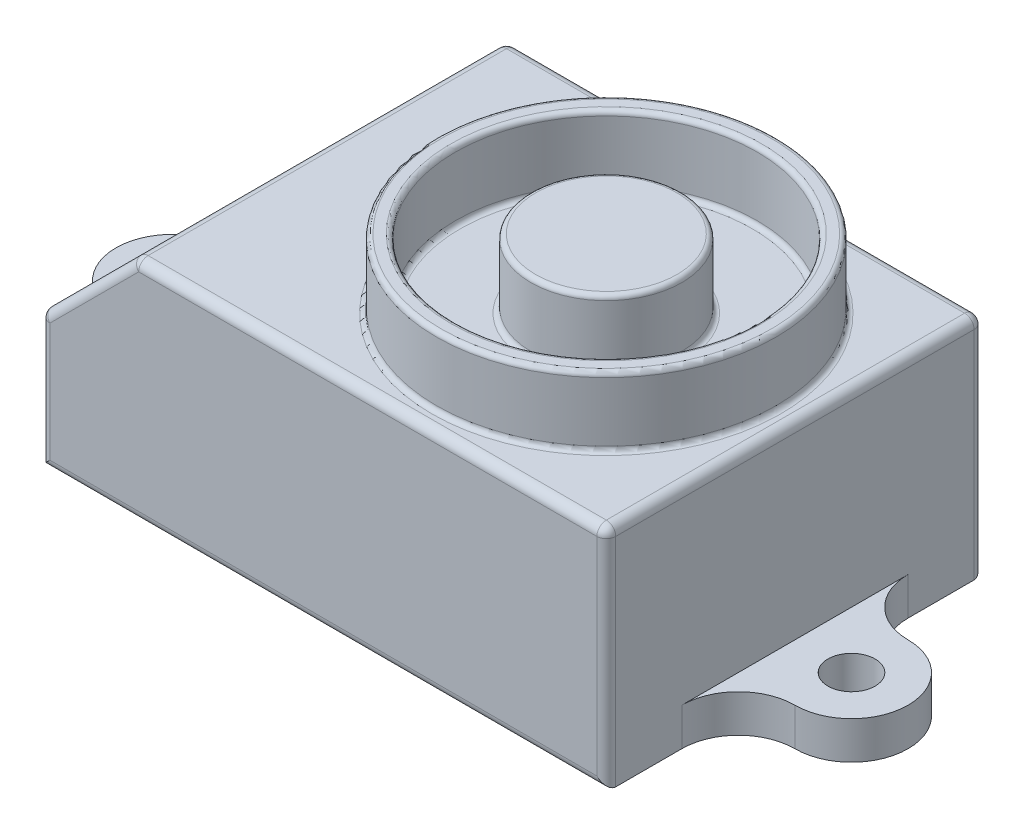
SolidWorks part; units mm, degrees
material "AISI 304"
ref_plane "Plano frontal" through (0, 0, 0) normal (0, 0, 1) x (1, 0, 0)
ref_plane "Plano superior" through (0, 0, 0) normal (0, 1, 0) x (1, 0, 0)
ref_plane "Plano direito" through (0, 0, 0) normal (1, 0, 0) x (0, 0, -1)
sketch "Esboço1" plane through (0, 0, 0) normal (0, 1, 0) x (1, 0, 0)
  line L0 (0, 15.4127) -> (0, -21.5735) construction
  line L1 (-15, 10) -> (15, 10)
  line L2 (-15, 10) -> (-15, -10)
  line L3 (-15, -10) -> (15, -10)
  line L4 (15, 10) -> (15, -10)
  line L5 (-15, 10) -> (15, -10) construction
  line L6 (-15, -10) -> (15, 10) construction
  line L7 (-34.0148, 0) -> (34.7521, 0) construction
  arc A0 (-18, 3) -> (-18, -3) centre (-18, 0) ccw
  circle A1 centre (-18, 0) radius 1.25
  arc A2 (-15, 6) -> (-18, 3) centre (-18, 6) cw
  arc A3 (-15, -6) -> (-18, -3) centre (-18, -6) ccw
  circle A4 centre (18, 0) radius 1.25
  arc A5 (15, -6) -> (18, -3) centre (18, -6) cw
  arc A6 (18, 3) -> (18, -3) centre (18, 0) cw
  arc A7 (15, 6) -> (18, 3) centre (18, 6) ccw
  circle A8 centre (5, 0) radius 4
  circle A9 centre (5, 0) radius 8
  circle A10 centre (5, 0) radius 9
  point P0 (0, 0)
  dimension "D3" = 6
  dimension "D4" = 2.5
  dimension "D5" = 3
  dimension "D6" = 3
  dimension "D7" = 8
  dimension "D8" = 16
  dimension "D9" = 18
  dimension "D10" = 10
  dimension "D1" = 30
  dimension "D2" = 20
extrude "Ressalto-extrusão1" add sketch "Esboço1" along normal blind 12 contours L4 L1 L2 L3 A10 region at (0, 0, -9.6394)
extrude "Ressalto-extrusão2" add sketch "Esboço1<3>" along normal blind 15.65 contours A10 A9 | A9 A8 | A8 region at (5, 0, 0) region at (-2.7737, 0, 0) region at (-3.7454, 0, 0)
sketch "Esboço1<3>" plane through (0, 0, 0) normal (0, 1, 0) x (1, 0, 0) same geometry as "Esboço1"
extrude "Ressalto-extrusão3" add sketch "Esboço1<4>" along normal blind 2 contours A3 L2 A2 A0 A1 | A1 | A7 L4 A5 A6 A4 | A4 region at (-15.1342, 0, 0) region at (15.7838, 0, -3.7838) region at (-18, 0, 0) region at (18, 0, 0)
sketch "Esboço1<4>" plane through (0, 0, 0) normal (0, 1, 0) x (1, 0, 0) same geometry as "Esboço1"
extrude "Corte-extrusão1" cut sketch "Esboço1<5>" along normal blind 2 contours A4 | A1 region at (-18, 0, 0) region at (18, 0, 0)
sketch "Esboço1<5>" plane through (0, 0, 0) normal (0, 1, 0) x (1, 0, 0) same geometry as "Esboço1"
extrude "Corte-extrusão2" cut sketch "Esboço1<6>" against normal blind 3.65 from surface contours A9 A8 region at (-2.7737, 0, 0) starting at face at (5, 15.65, 9)
sketch "Esboço1<6>" plane through (0, 0, 0) normal (0, 1, 0) x (1, 0, 0) same geometry as "Esboço1"
chamfer "Chanfro1" distance 5 angle 45 1 edges at (-15, 12, 0)
fillet "Filete1" radius 0.5 13 edges at (15, 6, 10) (0, 0, 10) (-15, 3.5, 10) (-12.5, 9.5, 10) (2.5, 12, 10) (15, 12, 0) (15, 6, -10) (0, 0, -10) (2.5, 12, -10) (-15, 3.5, -10) (-12.5, 9.5, -10) (-15, 7, 0) (-10, 12, 0)
fillet "Filete2" radius 0.25 6 edges at (5, 12, 4) (5, 12, 8) (5, 12, 9) (5, 15.65, 9) (5, 15.65, 8) (5, 15.65, 4)
